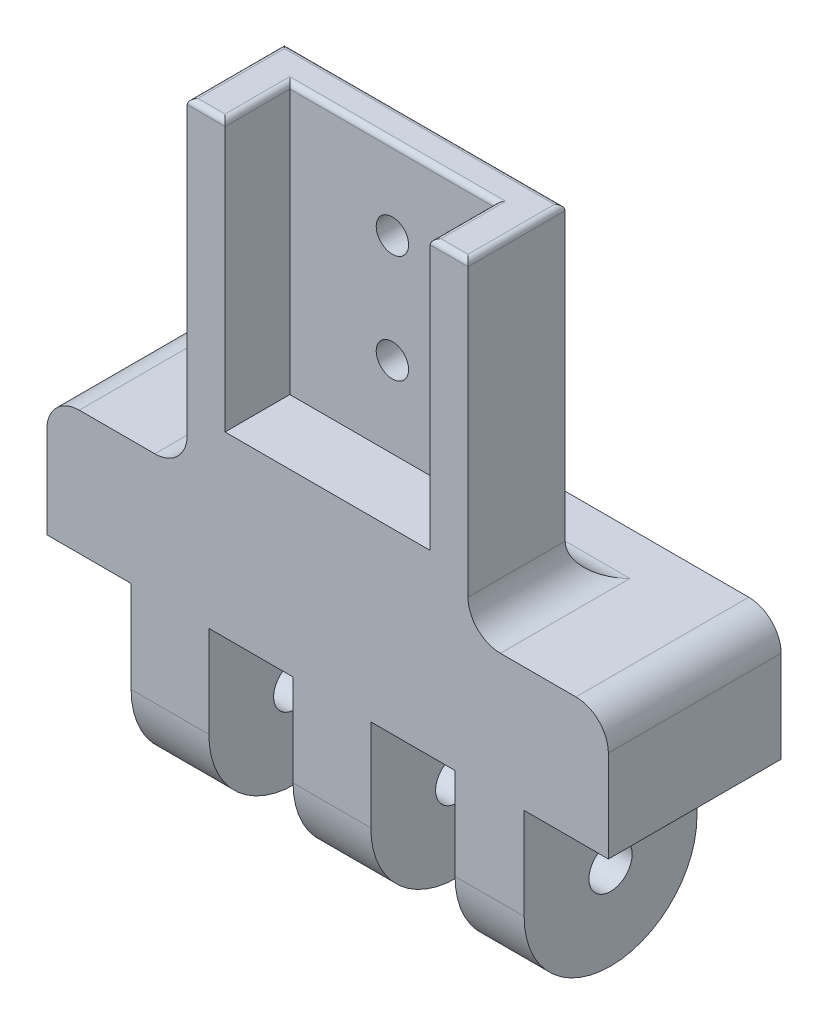
SolidWorks part; units mm, degrees
ref_plane "Front Plane" through (0, 0, 0) normal (0, 0, 1) x (1, 0, 0)
ref_plane "Top Plane" through (0, 0, 0) normal (0, 1, 0) x (1, 0, 0)
ref_plane "Right Plane" through (0, 0, 0) normal (1, 0, 0) x (0, 0, -1)
sketch "Sketch2" plane through (0, 0, 0) normal (1, 0, 0) x (0, 0, -1)
  line L2 (-8, 0) -> (-8, 20)
  line L3 (-8, 20) -> (8, 20)
  line L4 (8, 0) -> (8, 20)
  circle A0 centre (0, 0) radius 2
  arc A1 (-8, 0) -> (8, 0) centre (0, 0) ccw
  dimension "D1" = 16
  dimension "D2" = 4
  dimension "D3" = 20
extrude "Boss-Extrude1" add sketch "Sketch2" along normal mid plane 52
sketch "Sketch3" plane through (0, 0, 8) normal (0, 0, 1) x (1, 0, 0)
  line L0 (26, 0) -> (-26, 0) construction
  line L1 (-26, -8.5) -> (-18.2, -8.5)
  line L2 (-26, -8.5) -> (-26, 8.5)
  line L3 (-26, 8.5) -> (-18.2, 8.5)
  line L4 (-18.2, -8.5) -> (-18.2, 8.5)
  line L5 (-26, -8.5) -> (-18.2, 8.5) construction
  line L6 (-26, 8.5) -> (-18.2, -8.5) construction
  line L8 (-11, -8.5) -> (-3.2, -8.5)
  line L9 (-11, -8.5) -> (-11, 8.5)
  line L10 (-11, 8.5) -> (-3.2, 8.5)
  line L11 (-3.2, -8.5) -> (-3.2, 8.5)
  line L12 (-11, -8.5) -> (-3.2, 8.5) construction
  line L13 (-11, 8.5) -> (-3.2, -8.5) construction
  line L14 (4, -8.5) -> (11.8, -8.5)
  line L15 (4, -8.5) -> (4, 8.5)
  line L16 (4, 8.5) -> (11.8, 8.5)
  line L17 (11.8, -8.5) -> (11.8, 8.5)
  line L18 (4, -8.5) -> (11.8, 8.5) construction
  line L19 (4, 8.5) -> (11.8, -8.5) construction
  line L20 (-26, 20) -> (-26, 0) construction
  line L21 (26, 20) -> (26, 0) construction
  line L22 (18.2, -8.5) -> (26, -8.5)
  line L23 (18.2, -8.5) -> (18.2, 8.5)
  line L24 (18.2, 8.5) -> (26, 8.5)
  line L25 (26, -8.5) -> (26, 8.5)
  line L26 (18.2, -8.5) -> (26, 8.5) construction
  line L27 (18.2, 8.5) -> (26, -8.5) construction
  point P0 (-22.1, 0)
  point P7 (-7.1, 0)
  point P12 (7.9, 0)
  point P17 (-22.1, 8.5)
  point P20 (22.1, 0)
  dimension "D1" = 8.5
  dimension "D3" = 7.8
  dimension "D4" = 7.2
  dimension "D6" = 7.2
extrude "Cut-Extrude1" cut sketch "Sketch3" against normal through all
ref_plane "Plane1" through (0, 20, 0) normal (0, 1, 0) x (1, 0, 0)
sketch "Sketch5" plane through (0, 20, 0) normal (0, 1, 0) x (1, 0, 0)
  line L0 (26, -8) -> (-26, -8) construction
  line L1 (-13, -8) -> (13, -8)
  line L2 (-13, -8) -> (-13, 1)
  line L3 (-13, 1) -> (13, 1)
  line L4 (13, -8) -> (13, 1)
  line L5 (-13, -8) -> (13, 1) construction
  line L6 (-13, 1) -> (13, -8) construction
  line L8 (26, 8) -> (26, -8) construction
  point P0 (0, -3.5)
  point P7 (0, 0)
  point P10 (0, 0)
  dimension "D1" = 9
  dimension "D2" = 26
  dimension "D3" = 26
extrude "Boss-Extrude2" add sketch "Sketch5" along normal blind 30
ref_plane "Plane2" through (0, 50, 0) normal (0, 1, 0) x (1, 0, 0)
sketch "Sketch6" plane through (0, 50, 0) normal (0, 1, 0) x (1, 0, 0)
  line L0 (-13, -8) -> (13, -8) construction
  line L1 (-9.5, -2) -> (9.5, -2)
  line L2 (-9.5, -2) -> (-9.5, -8)
  line L3 (-9.5, -8) -> (9.5, -8)
  line L4 (9.5, -2) -> (9.5, -8)
  line L5 (-9.5, -2) -> (9.5, -8) construction
  line L6 (-9.5, -8) -> (9.5, -2) construction
  line L7 (13, -8) -> (13, 1) construction
  point P0 (0, -5)
  dimension "D1" = 19
  dimension "D2" = 13
  dimension "D3" = 6
extrude "Cut-Extrude2" cut sketch "Sketch6" against normal blind 25
sketch "Sketch7" plane through (0, 0, 0) normal (0, 0, 1) x (1, 0, 0)
  line L0 (9.5, 25) -> (9.5, 50) construction
  line L1 (-17.3915, 37.5) -> (25.6524, 37.5) construction
  line L2 (9.5, 25) -> (-9.5, 25) construction
  circle A0 centre (0, 42.5) radius 1.5
  circle A1 centre (0, 32.5) radius 1.5
  point P10 (0, 0)
  dimension "D1" = 3
  dimension "D2" = 10
  dimension "D3" = 9.5
  dimension "D4" = 5
  dimension "D5" = 12.5
extrude "Cut-Extrude3" cut sketch "Sketch7" against normal mid plane 25
fillet "Fillet2" radius 3 3 edges at (13, 20, 3.5) (0, 20, -1) (-13, 20, 3.5)
fillet "Fillet3" radius 3 2 edges at (-26, 20, 0) (26, 20, 0)
fillet "Fillet4" radius 0.5 8 edges at (11.25, 50, 8) (13, 50, 3.5) (9.5, 50, 5) (-11.25, 50, 8) (-9.5, 50, 5) (0, 50, 2) (-13, 50, 3.5) (0, 50, -1)
equation "\"hingewidth\"=7.2"
equation "\"fingerwidth\"=10.5"
equation "\"gapwidth\"=7.8"
equation "\"D3@Sketch3\"=\"gapwidth\""
equation "\"D4@Sketch3\"=\"hingewidth\""
equation "\"D6@Sketch3\"=\"hingewidth\""
